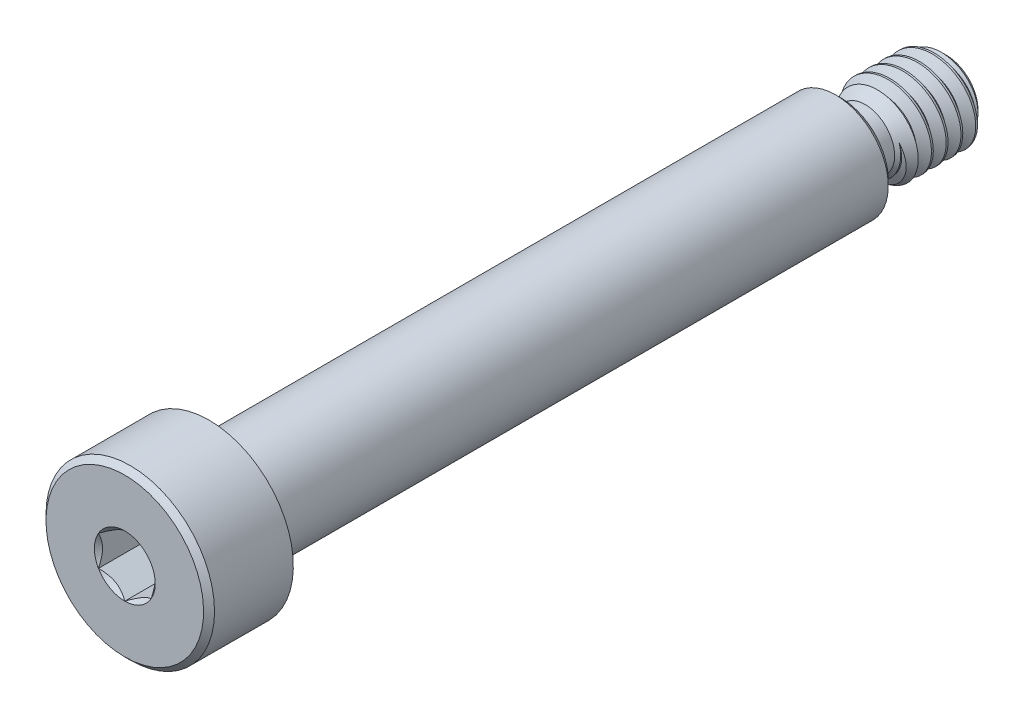
SolidWorks part; units mm, degrees
material "AISI Type 316L stainless steel"
ref_plane "Front" through (0, 0, 0) normal (0, 0, 1) x (1, 0, 0)
ref_plane "Top" through (0, 0, 0) normal (0, 1, 0) x (1, 0, 0)
ref_plane "Right" through (0, 0, 0) normal (1, 0, 0) x (0, 0, -1)
sketch "Sketch1" plane through (0, 0, 0) normal (1, 0, 0) x (0, 0, -1)
  line L0 (0, 4) -> (4, 4)
  line L1 (4, 4) -> (4, 2.5)
  line L2 (4, 2.5) -> (34, 2.5)
  line L3 (34, 2.5) -> (34, 2)
  line L4 (34, 2) -> (39, 2)
  line L5 (39, 2) -> (39, 0)
  line L6 (39, 0) -> (0, 0)
  line L7 (0, 0) -> (0, 4)
  line L8 (0, 4) -> (0, -4) construction
  line L9 (39, 2) -> (39, -2) construction
  line L10 (34, 2.5) -> (34, -2.5) construction
  point P8 (36.55, -2)
  point P12 (34, 0)
  dimension "Shoulder Dia" = 5
  dimension "Shoulder Lg" = 30
  dimension "D1" = 2.45
revolve "Revolve1" add sketch "Sketch1" angle 360 mid plane about L6
ref_plane "Plane1" through (0, 0, -39) normal (0, 0, 1) x (1, 0, 0)
sketch "Sketch3" plane through (0, 0, -39) normal (0, 0, 1) x (1, 0, 0)
  circle A0 centre (0, 0) radius 2
curve "Helix/Spiral1" pitch 0.7 height 5.7 radius 2 centre (0, 0, -39) axis (0, 0, 1) start towards (0, 1, 0)
sketch "Sketch5" plane through (0, 0, 0) normal (1, 0, 0) x (0, 0, -1)
  line L0 (34, 2.5) -> (36.243, 2.5)
  line L1 (36.243, 2.5) -> (35.143, 1.4)
  line L2 (35.143, 1.4) -> (34.6, 1.4)
  line L3 (34, 2.5) -> (34, 2)
  line L5 (34, 2) -> (39, 2) construction
  line L6 (39, 0) -> (35.143, 0) construction
  line L7 (37.0715, 0) -> (37.0715, -2) construction
  arc A0 (34, 2) -> (34.6, 1.4) centre (34.6, 2) ccw
  dimension "D1" = 45
  dimension "CADB" = 1.143
  dimension "CADA" = 2.8
revolve "Cut-Revolve1" cut sketch "Sketch5" angle 360 mid plane about L6
chamfer "Chamfer1" distance 0.5 angle 45 1 edges at (0, 2, -39)
chamfer "Chamfer2" distance 0.26 angle 45 2 edges at (0, 4, 0) (0, 2.5, -34)
sketch "Sketch8" plane through (0, 0, 0) normal (0, 0, 1) x (1, 0, 0)
  line L1 (1.25, 0.7217) -> (0, 1.4434)
  line L2 (0, 1.4434) -> (-1.25, 0.7217)
  line L3 (-1.25, 0.7217) -> (-1.25, -0.7217)
  line L4 (-1.25, -0.7217) -> (0, -1.4434)
  line L5 (0, -1.4434) -> (1.25, -0.7217)
  line L6 (1.25, -0.7217) -> (1.25, 0.7217)
  circle A0 centre (0, 0) radius 1.25 construction
  dimension "Hex" = 2.5
extrude "Cut-Extrude2" cut sketch "Sketch8" against normal blind 2
sketch "Sketch9" plane through (0, 0, 0) normal (0, 0, 1) x (1, 0, 0)
  circle A0 centre (0, 0) radius 1.4434
extrude "Cut-Extrude4" cut sketch "Sketch9" against normal blind 2 draft 45
sketch "Sketch4" plane through (0, 0, 0) normal (1, 0, 0) x (0, 0, -1)
  line L0 (39, 2) -> (39.6125, 2)
  line L1 (39.6125, 2) -> (39.35, 1.5453)
  line L2 (39.35, 1.5453) -> (39.2625, 1.5453)
  line L3 (39.2625, 1.5453) -> (39, 2)
  line L4 (39.1313, 1.7727) -> (39.4813, 1.7727) construction
  dimension "D1" = 0.0875
  dimension "D2" = 0.35
  dimension "D3" = 60
sweep "Sweep1" add profiles "Sketch4" path "Helix/Spiral1"
sketch "Sketch6" plane through (0, 0, -34) normal (0, 0, -1) x (-1, 0, 0)
  circle A1 centre (0, 0) radius 2.24
  circle A2 centre (0, 0) radius 2.24
  dimension "D1" = 0
extrude "Cut-Extrude1" cut sketch "Sketch6" against normal through all from vertex starting at point (0, 1.4, -34.6)
combine bodies "Combine1" operation type subtract main body 118 bodies to subtract 110
sketch "reference 1" plane through (0, 0, -4) normal (0, 0, -1) x (-1, 0, 0)
  circle A1 centre (0, 0) radius 4
  circle A2 centre (0, 0) radius 4 construction
equation "\"D3@Helix/Spiral1\" = \"Thread Lg@Sketch1\" + \"D4@Helix/Spiral1\""
equation "\"D1@Sketch4\" = \"D4@Helix/Spiral1\" * .125"
equation "\"D2@Sketch4\" = \"D4@Helix/Spiral1\" * .5"
equation "\"D1@Chamfer1\" = \"Thread Dia@Sketch1\" * .125"
equation "\"D1@Cut-Extrude2\"= \"Head Ht@Sketch1\" * .5"
equation "\"D1@Cut-Extrude4\" = \"D1@Cut-Extrude2\""
equation "\"D1@Chamfer2\" = \"Head Dia@Sketch1\" * .0325"
equation "\"D1@Sketch1\"=\"D4@Helix/Spiral1\"*3.5"
